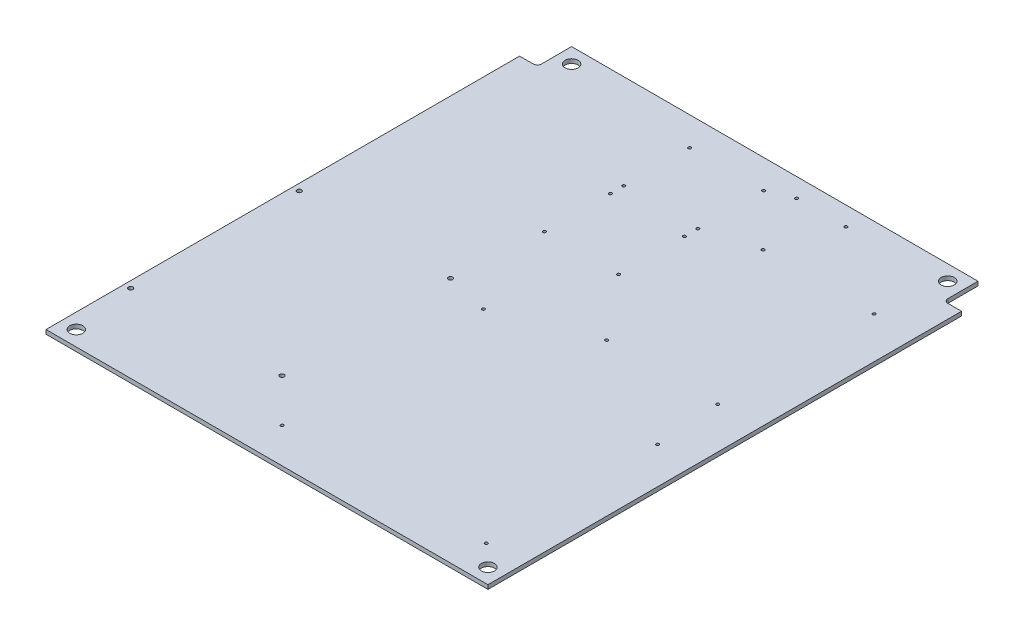
SolidWorks part; units mm, degrees
material "6061-T6 (SS)"
ref_plane "Front" through (0, 0, 0) normal (0, 0, 1) x (1, 0, 0)
ref_plane "Top" through (0, 0, 0) normal (0, 1, 0) x (1, 0, 0)
ref_plane "Right" through (0, 0, 0) normal (1, 0, 0) x (0, 0, -1)
sketch "Sketch1" plane through (0, 0, 0) normal (0, 1, 0) x (1, 0, 0)
  line L1 (170.434, -195.834) -> (-170.434, -195.834)
  line L2 (170.434, -195.834) -> (170.434, 195.834)
  line L3 (170.434, 195.834) -> (-170.434, 195.834)
  line L4 (-170.434, -195.834) -> (-170.434, 195.834)
  line L5 (170.434, -195.834) -> (-170.434, 195.834) construction
  line L6 (170.434, 195.834) -> (-170.434, -195.834) construction
  point P0 (0, 0)
  dimension "D1" = 340.868
  dimension "D2" = 391.668
extrude "Boss-Extrude1" add sketch "Sketch1" along normal blind 3.175
sketch "Sketch2" plane through (0, 3.175, 0) normal (0, 1, 0) x (1, 0, 0)
  line L0 (170.434, 195.834) -> (-170.434, 195.834) construction
  line L1 (-170.434, 195.834) -> (-156.718, 195.834)
  line L2 (-170.434, 195.834) -> (-170.434, 169.418)
  line L3 (-170.434, 169.418) -> (-159.893, 169.418)
  line L4 (-156.718, 195.834) -> (-156.718, 172.593)
  line L5 (170.434, 195.834) -> (156.718, 195.834)
  line L6 (170.434, 195.834) -> (170.434, 169.418)
  line L7 (170.434, 169.418) -> (159.893, 169.418)
  line L8 (156.718, 195.834) -> (156.718, 172.593)
  arc A0 (-156.718, 172.593) -> (-159.893, 169.418) centre (-159.893, 172.593) cw
  arc A1 (156.718, 172.593) -> (159.893, 169.418) centre (159.893, 172.593) ccw
  dimension "D1" = 3.175
  dimension "D2" = 26.416
  dimension "D3" = 13.716
extrude "Cut-Extrude1" cut sketch "Sketch2" against normal blind 10
hole_wizard "3/8 Clearance Hole1" positions "Sketch3" profile "Sketch4" hole size "3/8" standard "ANSI Inch"
sketch "Sketch3" plane through (0, 3.175, 0) normal (0, 1, 0) x (1, 0, 0)
  line L0 (158.75, -184.15) -> (0, -184.15) construction
  line L1 (0, -184.15) -> (-158.75, -184.15) construction
  line L2 (-158.75, -184.15) -> (-158.75, -13.208) construction
  line L3 (-158.75, -13.208) -> (-158.75, 157.734) construction
  line L4 (-158.75, 157.734) -> (158.75, 157.734) construction
  line L5 (158.75, 157.734) -> (158.75, -13.208) construction
  line L6 (158.75, -13.208) -> (158.75, -184.15) construction
  line L8 (145.034, 184.15) -> (0, 184.15) construction
  line L9 (0, 184.15) -> (-145.034, 184.15) construction
  line L10 (-145.034, 184.15) -> (-156.718, 195.834) construction
  line L12 (156.718, 195.834) -> (145.034, 184.15) construction
  line L14 (-158.75, 157.734) -> (-170.434, 169.418) construction
  line L16 (-158.75, -184.15) -> (-170.434, -195.834) construction
  line L18 (158.75, 157.734) -> (170.434, 169.418) construction
  line L20 (158.75, -184.15) -> (170.434, -195.834) construction
  line L21 (158.75, -184.15) -> (158.75, -195.834) construction
  line L22 (-170.434, -195.834) -> (170.434, -195.834) construction
  line L24 (158.75, -184.15) -> (170.434, -184.15) construction
  line L25 (170.434, -195.834) -> (170.434, 169.418) construction
  point P0 (158.75, -184.15)
  point P2 (-158.75, -184.15)
  point P94 (-145.034, 184.15)
  point P96 (145.034, 184.15)
  point P110 (0, 0)
  point P111 (0, 0)
  point P112 (0, 0)
  point P113 (0, 0)
  point P114 (0, 0)
  dimension "D1" = 11.684
sketch "Sketch4" plane through (158.75, 3.175, 184.15) normal (1, 0, 0) x (0, 0, 1)
  line L0 (0, 0) -> (0, 21.7795)
  line L1 (0, 21.7795) -> (5.0419, 18.75)
  line L2 (5.0419, 18.75) -> (5.0419, 0)
  line L5 (5.0419, 0) -> (0, 0)
  line L10 (0, 21.7795) -> (-5.0419, 18.75) construction
  line L11 (0, -6.35) -> (0, 107.95) construction
  dimension "Hole Dia." = 10.0838
  dimension "Hole Depth" = 18.75
  dimension "Drill Angle" = 118
hole_wizard "#4-40 Tapped Hole1" positions "Sketch5" profile "Sketch6" tap size "#4-40" standard "ANSI Inch"
sketch "Sketch5" plane through (0, 3.175, 0) normal (0, 1, 0) x (1, 0, 0)
  point P0 (-15.34, -13.51)
  point P3 (142.14, -36.73)
  point P6 (142.14, -168.81)
  point P9 (-15.34, -168.81)
  point P12 (-43.575, 61.759)
  point P15 (13.575, 61.759)
  point P18 (13.575, 112.559)
  point P21 (-43.575, 112.559)
  point P24 (-43.575, 122.909)
  point P27 (-43.575, 173.709)
  point P30 (13.575, 173.709)
  point P33 (13.575, 122.909)
sketch "Sketch6" plane through (-15.34, 3.175, 13.51) normal (1, 0, 0) x (0, 0, 1)
  line L0 (0, 0) -> (0, 8.2792)
  line L1 (0, 8.2792) -> (1.1303, 7.6)
  line L2 (1.1303, 7.6) -> (1.1303, 0)
  line L5 (1.1303, 0) -> (0, 0)
  line L10 (0, 8.2792) -> (-1.1303, 7.6) construction
  line L11 (0, -6.35) -> (0, 107.95) construction
  dimension "Tap Drill Dia." = 2.2606
  dimension "Tap Drill Depth" = 7.6
  dimension "Drill Angle" = 118
cosmetic thread "Hole Thread1" parameters "D1"=3.175, "D2"=2.8448
cosmetic thread "Hole Thread2" parameters "D1"=3.175, "D2"=2.8448
cosmetic thread "Hole Thread3" parameters "D1"=3.175, "D2"=2.8448
cosmetic thread "Hole Thread4" parameters "D1"=3.175, "D2"=2.8448
cosmetic thread "Hole Thread9" parameters "D1"=3.175, "D2"=2.8448
cosmetic thread "Hole Thread10" parameters "D1"=3.175, "D2"=2.8448
cosmetic thread "Hole Thread11" parameters "D1"=3.175, "D2"=2.8448
cosmetic thread "Hole Thread12" parameters "D1"=3.175, "D2"=2.8448
cosmetic thread "Hole Thread13" parameters "D1"=3.175, "D2"=2.8448
cosmetic thread "Hole Thread14" parameters "D1"=3.175, "D2"=2.8448
cosmetic thread "Hole Thread15" parameters "D1"=3.175, "D2"=2.8448
cosmetic thread "Hole Thread16" parameters "D1"=3.175, "D2"=2.8448
hole_wizard "#8-32 Tapped Hole1" positions "Sketch7" profile "Sketch8" tap size "#8-32" standard "ANSI Inch"
sketch "Sketch7" plane through (0, 3.175, 0) normal (0, 1, 0) x (1, 0, 0)
  arc A0 (-165.334, -7.875) -> (-165.334, -3.375) centre (-165.334, -5.625) ccw construction
  arc A1 (-165.334, -137.875) -> (-165.334, -133.375) centre (-165.334, -135.625) ccw construction
  arc A2 (-48.634, -3.375) -> (-48.634, -7.875) centre (-48.634, -5.625) ccw construction
  arc A3 (-48.634, -133.375) -> (-48.634, -137.875) centre (-48.634, -135.625) ccw construction
  point P0 (-165.334, -5.625)
  point P2 (-165.334, -135.625)
  point P5 (-48.634, -135.625)
  point P9 (-48.634, -5.625)
  point P16 (0, 0)
sketch "Sketch8" plane through (-165.334, 3.175, 5.625) normal (1, 0, 0) x (0, 0, 1)
  line L0 (0, 0) -> (0, 11.7478)
  line L1 (0, 11.7478) -> (1.7272, 10.71)
  line L2 (1.7272, 10.71) -> (1.7272, 0)
  line L5 (1.7272, 0) -> (0, 0)
  line L10 (0, 11.7478) -> (-1.7272, 10.71) construction
  line L11 (0, -6.35) -> (0, 107.95) construction
  dimension "Tap Drill Dia." = 3.4544
  dimension "Tap Drill Depth" = 10.71
  dimension "Drill Angle" = 118
cosmetic thread "Hole Thread5" parameters "D1"=3.175, "D2"=4.1656
cosmetic thread "Hole Thread6" parameters "D1"=3.175, "D2"=4.1656
cosmetic thread "Hole Thread7" parameters "D1"=3.175, "D2"=4.1656
cosmetic thread "Hole Thread8" parameters "D1"=3.175, "D2"=4.1656
hole_wizard "#4-40 Tapped Hole2" positions "Sketch9" profile "Sketch10" tap size "#4-40" standard "ANSI Inch"
sketch "Sketch9" plane through (0, 3.175, 0) normal (0, 1, 0) x (1, 0, 0)
  circle A0 centre (52.859, 133.909) radius 1.6319 construction
  circle A1 centre (138.509, 133.909) radius 1.6319 construction
  circle A2 centre (138.509, 13.259) radius 1.6319 construction
  circle A3 centre (52.859, 13.259) radius 1.6319 construction
  point P0 (138.509, 13.259)
  point P2 (52.859, 13.259)
  point P4 (138.509, 133.909)
  point P6 (52.859, 133.909)
  point P13 (0, 0)
sketch "Sketch10" plane through (138.509, 3.175, -13.259) normal (1, 0, 0) x (0, 0, 1)
  line L0 (0, 0) -> (0, 8.2792)
  line L1 (0, 8.2792) -> (1.1303, 7.6)
  line L2 (1.1303, 7.6) -> (1.1303, 0)
  line L5 (1.1303, 0) -> (0, 0)
  line L10 (0, 8.2792) -> (-1.1303, 7.6) construction
  line L11 (0, -6.35) -> (0, 107.95) construction
  dimension "Tap Drill Dia." = 2.2606
  dimension "Tap Drill Depth" = 7.6
  dimension "Drill Angle" = 118
cosmetic thread "Hole Thread17" parameters "D1"=3.175, "D2"=2.8448
cosmetic thread "Hole Thread18" parameters "D1"=3.175, "D2"=2.8448
cosmetic thread "Hole Thread19" parameters "D1"=3.175, "D2"=2.8448
cosmetic thread "Hole Thread20" parameters "D1"=3.175, "D2"=2.8448
hole_wizard "#4-40 Tapped Hole3" positions "Sketch11" profile "Sketch12" tap size "#4-40" standard "ANSI Inch"
sketch "Sketch11" plane through (0, 3.175, 0) normal (0, 1, 0) x (1, 0, 0)
  point P0 (69.434, 181.209)
  point P3 (31.434, 181.209)
sketch "Sketch12" plane through (69.434, 3.175, -181.209) normal (1, 0, 0) x (0, 0, 1)
  line L0 (0, 0) -> (0, 8.2792)
  line L1 (0, 8.2792) -> (1.1303, 7.6)
  line L2 (1.1303, 7.6) -> (1.1303, 0)
  line L5 (1.1303, 0) -> (0, 0)
  line L10 (0, 8.2792) -> (-1.1303, 7.6) construction
  line L11 (0, -6.35) -> (0, 107.95) construction
  dimension "Tap Drill Dia." = 2.2606
  dimension "Tap Drill Depth" = 7.6
  dimension "Drill Angle" = 118
cosmetic thread "Hole Thread21" parameters "D1"=3.175, "D2"=2.8448
cosmetic thread "Hole Thread22" parameters "D1"=3.175, "D2"=2.8448
